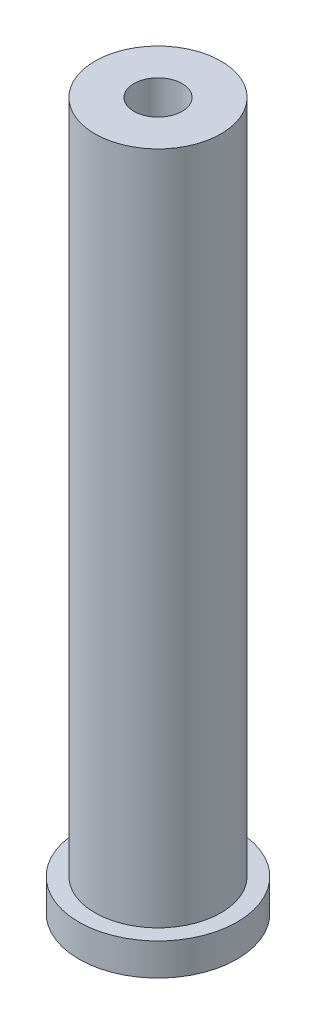
SolidWorks part; units mm, degrees
ref_plane "Ebene vorne" through (0, 0, 0) normal (0, 0, 1) x (1, 0, 0)
ref_plane "Ebene oben" through (0, 0, 0) normal (0, 1, 0) x (1, 0, 0)
ref_plane "Ebene rechts" through (0, 0, 0) normal (1, 0, 0) x (0, 0, -1)
sketch "Skizze1" plane through (0, 0, 0) normal (0, 1, 0) x (1, 0, 0)
  circle A0 centre (0, 0) radius 4.925
  dimension "D1" = 9.85
extrude "Aufsatz-Linear austragen1" add sketch "Skizze1" along normal blind 2
sketch "Skizze2" plane through (0, 2, 0) normal (0, 1, 0) x (1, 0, 0)
  circle A0 centre (0, 0) radius 3.925
  dimension "D1" = 7.85
extrude "Aufsatz-Linear austragen2" add sketch "Skizze2" along normal blind 42
sketch "Skizze3" plane through (0, 44, 0) normal (0, 1, 0) x (1, 0, 0)
  circle A0 centre (0, 0) radius 1.5
  dimension "D1" = 3
extrude "Schnitt-Linear austragen1" cut sketch "Skizze3" against normal blind 15
